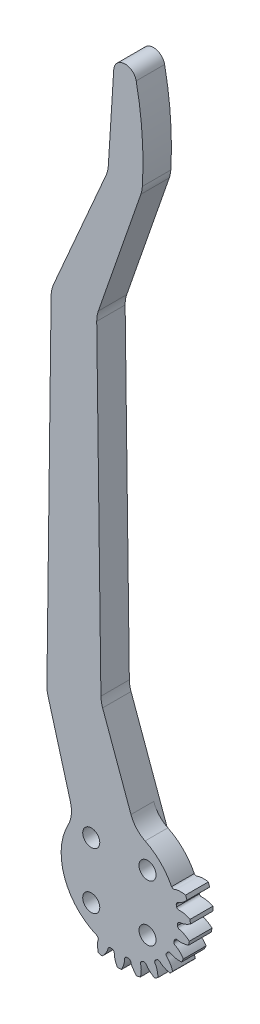
SolidWorks part; units mm, degrees
material "Thornel Mat VMA"
ref_plane "前视基准面" through (0, 0, 0) normal (0, 0, 1) x (1, 0, 0)
ref_plane "上视基准面" through (0, 0, 0) normal (0, 1, 0) x (1, 0, 0)
ref_plane "右视基准面" through (0, 0, 0) normal (1, 0, 0) x (0, 0, -1)
sketch "草图1" plane through (0, 0, 0) normal (0, 0, 1) x (1, 0, 0)
  circle A0 centre (0, 0) radius 12.5
extrude "凸台-拉伸1" add sketch "草图1" along normal blind 4
ref_axis "基准轴1" through (0, 0, 4) along (0, 0, -1)
sketch "草图2" plane through (0, 0, 0) normal (0, 0, 1) x (1, 0, 0)
  line L0 (0, 0) -> (0, 12.5) construction
  circle A0 centre (0, 0) radius 12.5 construction
  arc A1 (0.1814, 10.2484) -> (-0.1814, 10.2484) centre (0, 0) ccw
  arc A2 (3.1817, 14.1862) -> (-3.1817, 14.1862) centre (0, 0) ccw
  spline S0 degree 3 poles (0.1814, 10.2484) (0.5777, 10.3668) (0.5438, 10.6338) (0.5929, 10.8972) (0.5995, 10.9289) (0.6077, 10.9648) (0.6176, 11.0046) (0.6294, 11.0484) (0.6433, 11.0961) (0.6595, 11.1477) (0.6781, 11.203) (0.6992, 11.262) (0.723, 11.3247) (0.7498, 11.3908) (0.7795, 11.4604) (0.8124, 11.5333) (0.8485, 11.6094) (0.8882, 11.6887) (0.9314, 11.7709) (0.9783, 11.8561) (1.0291, 11.9441) (1.0839, 12.0347) (1.1428, 12.1279) (1.2059, 12.2235) (1.2734, 12.3214) (1.3454, 12.4214) (1.4219, 12.5234) (1.5031, 12.6273) (1.5891, 12.7328) (1.68, 12.84) (1.7759, 12.9485) (1.8768, 13.0583) (1.9829, 13.1691) (2.0943, 13.2809) (2.211, 13.3934) (2.3331, 13.5065) (2.4606, 13.62) (2.5937, 13.7338) (2.7324, 13.8476) (2.9271, 14.001) (3.0783, 14.1128) (3.1817, 14.1862) knots 0 0 0 0 0.147387 0.15296 0.159389 0.166677 0.174821 0.183823 0.193683 0.204399 0.215973 0.228404 0.241693 0.255839 0.270842 0.286703 0.303421 0.320996 0.339428 0.358718 0.378866 0.39987 0.421732 0.444451 0.468028 0.492462 0.517753 0.543901 0.570907 0.59877 0.627491 0.657069 0.687504 0.718796 0.750946 0.783953 0.817818 0.85254 0.888119 0.924555 1 1 1 1
  spline S1 degree 3 poles (-0.1814, 10.2484) (-0.5777, 10.3668) (-0.5438, 10.6338) (-0.5929, 10.8972) (-0.5995, 10.9289) (-0.6077, 10.9648) (-0.6176, 11.0046) (-0.6294, 11.0484) (-0.6433, 11.0961) (-0.6595, 11.1477) (-0.6781, 11.203) (-0.6992, 11.262) (-0.723, 11.3247) (-0.7498, 11.3908) (-0.7795, 11.4604) (-0.8124, 11.5333) (-0.8485, 11.6094) (-0.8882, 11.6887) (-0.9314, 11.7709) (-0.9783, 11.8561) (-1.0291, 11.9441) (-1.0839, 12.0347) (-1.1428, 12.1279) (-1.2059, 12.2235) (-1.2734, 12.3214) (-1.3454, 12.4214) (-1.4219, 12.5234) (-1.5031, 12.6273) (-1.5891, 12.7328) (-1.68, 12.84) (-1.7759, 12.9485) (-1.8768, 13.0583) (-1.9829, 13.1691) (-2.0943, 13.2809) (-2.211, 13.3934) (-2.3331, 13.5065) (-2.4606, 13.62) (-2.5937, 13.7338) (-2.7324, 13.8476) (-2.9271, 14.001) (-3.0783, 14.1128) (-3.1817, 14.1862) knots 0 0 0 0 0.147387 0.15296 0.159389 0.166677 0.174821 0.183823 0.193683 0.204399 0.215973 0.228404 0.241693 0.255839 0.270842 0.286703 0.303421 0.320996 0.339428 0.358718 0.378866 0.39987 0.421732 0.444451 0.468028 0.492462 0.517753 0.543901 0.570907 0.59877 0.627491 0.657069 0.687504 0.718796 0.750946 0.783953 0.817818 0.85254 0.888119 0.924555 1 1 1 1
extrude "切除-拉伸1" cut sketch "草图2" along normal through all
pattern_circular "阵列(圆周)1" count 23 every 15.652 about axis through (0, 0, 4) along (0, 0, -1) of "切除-拉伸1"
sketch "草图3" plane through (0, 0, 0) normal (0, 0, 1) x (1, 0, 0)
  circle A0 centre (0, 0) radius 11.5 construction
  dimension "Dn" = 23
sketch "草图4" plane through (0, 0, 4) normal (0, 0, 1) x (1, 0, 0)
  line L0 (0, 0) -> (4, 0) construction
  line L1 (4, 0) -> (4, 108) construction
  line L2 (0, 0) -> (-8, 25) construction
  line L3 (-8, 25) -> (-8, 85) construction
  line L4 (-8, 85) -> (1, 108) construction
  line L5 (-4, 85) -> (4, 108)
  line L6 (-12, 85) -> (-4, 85) construction
  line L7 (-12.7621, 23.4761) -> (-3.2379, 26.5239) construction
  line L8 (-5.7803, -1.6088) -> (-12.7621, 23.4761)
  line L9 (5.6404, 2.0458) -> (-3.2379, 26.5239)
  line L10 (-3.2379, 26.5239) -> (-4, 85)
  line L11 (-12.7621, 23.4761) -> (-12, 85)
  line L12 (-12, 85) -> (-2, 108)
  line L13 (-2, 108) -> (-0.9961, 123.9685)
  arc A0 (-5.7803, -1.6088) -> (5.6404, 2.0458) centre (0, 0) ccw
  arc A1 (2.9601, 124.2403) -> (-0.9961, 123.9685) centre (1, 123.843) ccw
  arc A3 (4, 108) -> (2.9601, 124.2403) centre (-55.8442, 112.3216) ccw
  arc A4 (-4.0977, 85) -> (-3.8039, 85.5638) centre (-55.8442, 112.3216) ccw
  dimension "D3" = 12
  dimension "D4" = 10
  dimension "D12" = 4
  dimension "D13" = 60
  dimension "D1" = 108
  dimension "D2" = 4
  dimension "D5" = 8
  dimension "D6" = 25
  dimension "D7" = 60
  dimension "D8" = 3
  dimension "D9" = 12
  dimension "D10" = 3
  dimension "D11" = 16
extrude "凸台-拉伸2" add sketch "草图4" against normal blind 5 contours L5 A3 A1 L13 L12 L11 L8 A0 L9 L10 region at (-5.1539, 51.5145, 4)
sketch "草图5" plane through (0, 0, 4) normal (0, 0, 1) x (1, 0, 0)
  line L1 (-4.0836, -9.4014) -> (-5.976, -13.7582)
  line L3 (9.1828, 4.5539) -> (13.4383, 6.6642)
  line L4 (-8.0086, 6.3973) -> (-9.4665, 11.6355)
  line L5 (-8.1329, 6.844) -> (-12.7621, 23.4761) construction
  line L6 (2.8069, 9.8582) -> (0.9529, 14.9697)
  line L10 (1.9014, 12.3545) -> (-3.2379, 26.5239) construction
  arc A0 (9.1828, 4.5539) -> (2.8069, 9.8582) centre (0, 0) ccw
  arc A1 (13.4383, 6.6642) -> (0.9529, 14.9697) centre (0, 0) ccw
  arc A2 (-9.4665, 11.6355) -> (-5.976, -13.7582) centre (0, 0) ccw
  arc A3 (-8.0086, 6.3973) -> (-4.0836, -9.4014) centre (0, 0) ccw
  arc A4 (-4.2493, -9.3277) -> (-3.9166, -9.4722) centre (0, 0) ccw construction
  dimension "D1" = 30
extrude "切除-拉伸2" cut sketch "草图5" against normal blind 10
fillet "圆角1" radius 5 8 edges at (-2, 108, 1.5) (4, 108, 1.5) (-4, 85, 1.5) (-12, 85, 1.5) (-12.7621, 23.4761, 1.5) (-3.2379, 26.5239, 1.5) (2.8069, 9.8582, 2) (-8.0086, 6.3973, 2)
sketch "草图6" plane through (0, 0, 4) normal (0, 0, 1) x (1, 0, 0)
  line L0 (0, 0) -> (7, 0) construction
  line L1 (0, 0) -> (4.9497, 4.9497) construction
  circle A0 centre (0, 0) radius 7
  circle A1 centre (4.9497, 4.9497) radius 1.5
  circle A2 centre (4.9497, -4.9497) radius 1.5
  circle A3 centre (-4.9497, -4.9497) radius 1.5
  circle A4 centre (-4.9497, 4.9497) radius 1.5
  point P15 (0, 0)
  dimension "D1" = 14
  dimension "D2" = 3
  dimension "D3" = 45
  dimension "D4" = 4
extrude "切除-拉伸3" cut sketch "草图6" against normal blind 10 contours A4 | A1 | A2 | A3
